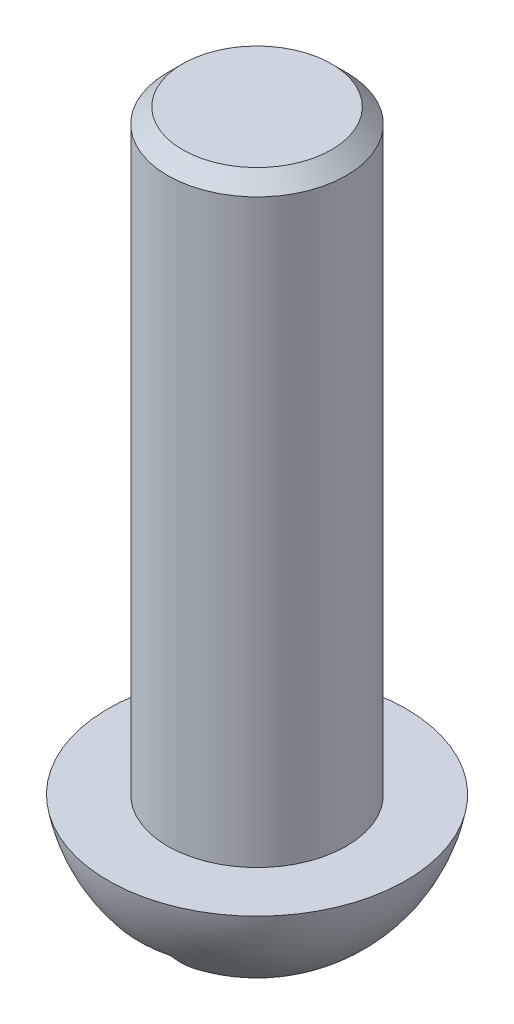
SolidWorks part; units mm, degrees
material "Plain Carbon Steel"
ref_plane "Спереди" through (0, 0, 0) normal (0, 0, 1) x (1, 0, 0)
ref_plane "Сверху" through (0, 0, 0) normal (0, 1, 0) x (1, 0, 0)
ref_plane "Справа" through (0, 0, 0) normal (1, 0, 0) x (0, 0, -1)
sketch "Sketch1" plane through (0, 0, 0) normal (0, 1, 0) x (1, 0, 0)
  circle A0 centre (0, 0) radius 3
  dimension "D1" = 6
extrude "Boss-Extrude1" add sketch "Sketch1" along normal blind 20
chamfer "Chamfer1" distance 0.5 angle 45 1 edges at (0, 20, 3)
sketch "Sketch2" plane through (0, 0, 0) normal (0, 0, 1) x (1, 0, 0)
  line L0 (0, 0) -> (-5, 0)
  line L1 (0, -4.2) -> (0, 0) construction
  line L2 (0, 0) -> (0, -4.2)
  arc A0 (-5, 0) -> (0, -4.2) centre (0.02, 0.9) ccw
  dimension "D3" = 5.1
  dimension "D1" = 5
  dimension "D2" = 4.2
revolve "Revolve1" add sketch "Sketch2" angle 360 about L1
sketch "Sketch3" plane through (0, 0, 0) normal (0, 0, 1) x (1, 0, 0)
  line L0 (-0.955, -2.29) -> (0, -2.29)
  line L1 (0, -2.29) -> (0.955, -2.29)
  line L2 (0.955, -2.29) -> (0.955, -6.2281)
  line L3 (0.955, -6.2281) -> (-0.955, -6.2281)
  line L4 (-0.955, -6.2281) -> (-0.955, -2.29)
  dimension "D1" = 2.29
  dimension "D2" = 1.91
extrude "Cut-Extrude1" cut sketch "Sketch3" against normal through all and the other way through all
